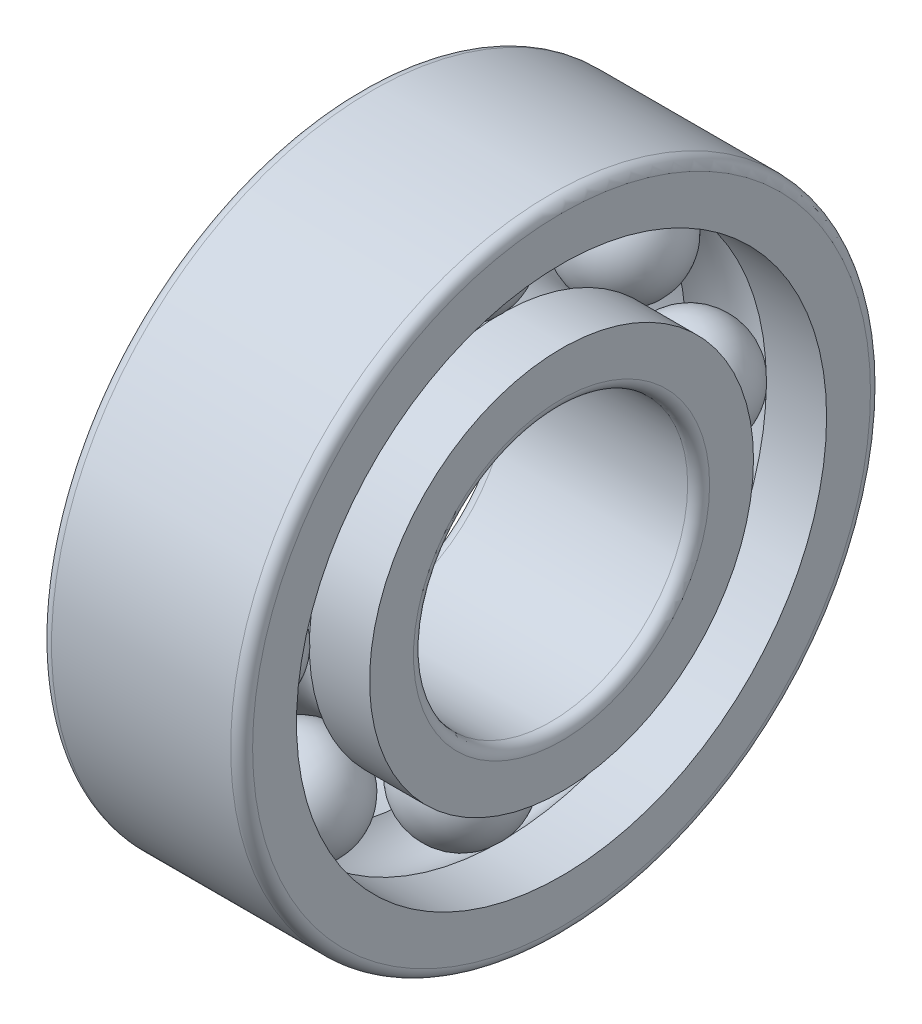
SolidWorks part; units mm, degrees
ref_plane "Plane1" through (0, 0, 0) normal (0, 0, 1) x (1, 0, 0)
ref_plane "Plane2" through (0, 0, 0) normal (0, 1, 0) x (1, 0, 0)
ref_plane "Plane3" through (0, 0, 0) normal (1, 0, 0) x (0, 0, -1)
ref_axis "Axis1" through (-50, 0, 0) along (1, 0, 0)
sketch "BalDetSke" plane through (0, 0, 0) normal (0, 0, 1) x (1, 0, 0)
  line L0 (-3, 12.5) -> (3, 12.5)
  line L1 (-1.905, 12.5) -> (1.905, 12.5) construction
  line L2 (0, 0) -> (0, 25) construction
  arc A0 (3, 12.5) -> (-3, 12.5) centre (0, 12.5) cw
  dimension "Ball_diameter" = 6
  dimension "BallCLRad" = 12.5
revolve "BallDetailed" add sketch "BalDetSke" angle 360 about L1 reverse direction yes
sketch "InnRacSke" plane through (0, 0, 0) normal (0, 0, 1) x (1, 0, 0)
  line L0 (-2.2024, 10.5) -> (-5.5, 10.5)
  line L1 (-5.5, 10.5) -> (-5.5, 8.1)
  line L2 (-4.9, 7.5) -> (4.9, 7.5)
  line L3 (5.5, 8.1) -> (5.5, 10.5)
  line L4 (5.5, 10.5) -> (2.2024, 10.5)
  line L5 (-20.6375, 0) -> (20.6375, 0) construction
  line L6 (0, 0) -> (0, 30) construction
  arc A0 (-5.5, 8.1) -> (-4.9, 7.5) centre (-4.9, 8.1) ccw
  arc A1 (4.9, 7.5) -> (5.5, 8.1) centre (4.9, 8.1) ccw
  arc A2 (2.2024, 10.5) -> (-2.2024, 10.5) centre (0, 12.5) cw
  dimension "Fillet_radius" = 0.6
  dimension "Ball_diameter" = 5.95
  dimension "ID" = 15
  dimension "OD" = 21
  dimension "Width" = 11
  dimension "BallCLRad" = 12.5
revolve "InnerRace" add sketch "InnRacSke" angle 360 about L5 reverse direction yes
sketch "OutRacSke" plane through (0, 0, 0) normal (0, 0, 1) x (1, 0, 0)
  line L0 (-2.2024, 14.5) -> (-5.5, 14.5)
  line L1 (-5.5, 14.5) -> (-5.5, 16.9)
  line L2 (-4.9, 17.5) -> (4.9, 17.5)
  line L3 (5.5, 16.9) -> (5.5, 14.5)
  line L4 (5.5, 14.5) -> (2.2024, 14.5)
  line L5 (-20.6375, 0) -> (20.6375, 0) construction
  line L6 (0, 0) -> (0, 30) construction
  arc A0 (-5.5, 16.9) -> (-4.9, 17.5) centre (-4.9, 16.9) cw
  arc A1 (4.9, 17.5) -> (5.5, 16.9) centre (4.9, 16.9) cw
  arc A2 (2.2024, 14.5) -> (-2.2024, 14.5) centre (0, 12.5) ccw
  dimension "Fillet_radius" = 0.6
  dimension "Ball_diameter" = 5.95
  dimension "OD" = 35
  dimension "ID" = 29
  dimension "Width" = 11
  dimension "BallCLRad" = 12.5
revolve "OuterRace" add sketch "OutRacSke" angle 360 about L5 reverse direction yes
pattern_circular "Répétition circulaire1" count 8 over 360 about axis through (-20.6375, 0, 0) along (1, 0, 0) of bodies 102
